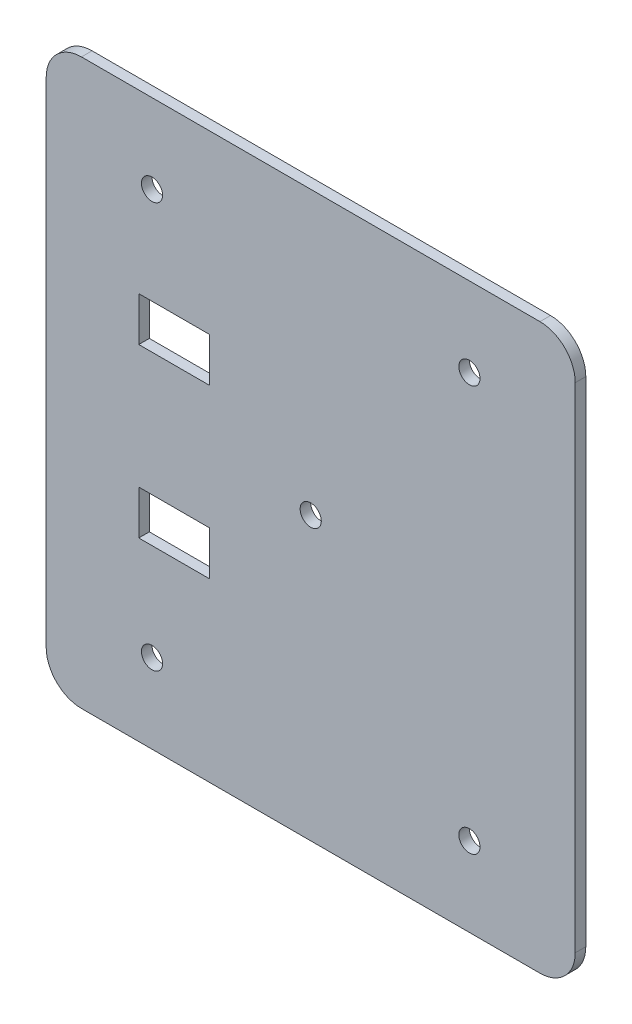
SolidWorks part; units mm, degrees
material "7075-T6, Plate (SS)"
ref_plane "Front Plane" through (0, 0, 0) normal (0, 0, 1) x (1, 0, 0)
ref_plane "Top Plane" through (0, 0, 0) normal (0, 1, 0) x (1, 0, 0)
ref_plane "Right Plane" through (0, 0, 0) normal (1, 0, 0) x (0, 0, -1)
sketch "Sketch1" plane through (0, 0, 0) normal (0, 0, 1) x (1, 0, 0)
  line L0 (-22.5, -22.5) -> (22.5, -22.5) construction
  line L1 (22.5, -22.5) -> (22.5, 22.5) construction
  line L2 (22.5, 22.5) -> (-22.5, 22.5) construction
  line L3 (-22.5, 22.5) -> (-22.5, -22.5) construction
  line L4 (22.5, 92.5) -> (22.5, 137.5) construction
  line L5 (22.5, 137.5) -> (-22.5, 137.5) construction
  line L6 (-22.5, 137.5) -> (-22.5, 92.5) construction
  line L7 (-22.5, 92.5) -> (22.5, 92.5) construction
  line L8 (-22.5, -22.5) -> (22.5, -22.5)
  line L9 (22.5, -22.5) -> (22.5, 22.5)
  line L10 (22.5, 22.5) -> (-22.5, 22.5)
  line L11 (-22.5, 22.5) -> (-22.5, -22.5)
  line L12 (22.5, 92.5) -> (22.5, 137.5)
  line L13 (22.5, 137.5) -> (-22.5, 137.5)
  line L14 (-22.5, 137.5) -> (-22.5, 92.5)
  line L15 (-22.5, 92.5) -> (22.5, 92.5)
  line L16 (-22.5, 92.5) -> (22.5, 137.5)
  line L17 (-22.5, 137.5) -> (22.5, 92.5)
  line L18 (22.5, 22.5) -> (-22.5, -22.5)
  line L19 (-22.5, 22.5) -> (22.5, -22.5)
  line L20 (75, -102.5) -> (75, 57.5)
  line L21 (-55, -102.5) -> (75, -102.5)
  line L22 (-75, -82.5) -> (-75, 197.5)
  line L23 (75, -102.5) -> (75, 217.5)
  line L24 (-55, 217.5) -> (75, 217.5)
  line L25 (-75, -102.5) -> (75, 217.5) construction
  line L26 (75, -102.5) -> (-75, 217.5) construction
  line L27 (0, 0) -> (0, 57.5)
  line L28 (75, -102.5) -> (75, 217.5)
  line L29 (75, -102.5) -> (205, -102.5)
  line L30 (75, 217.5) -> (205, 217.5)
  line L31 (225, -82.5) -> (225, 197.5)
  line L32 (165, 217.5) -> (165, 172.5)
  line L33 (165, 172.5) -> (225, 172.5)
  line L34 (225, -57.5) -> (165, -57.5)
  line L35 (165, -57.5) -> (165, -102.5)
  line L36 (-15, -102.5) -> (-15, -57.5)
  line L37 (-15, -57.5) -> (-75, -57.5)
  line L38 (-75, 172.5) -> (-15, 172.5)
  line L39 (-15, 172.5) -> (-15, 217.5)
  line L40 (-22.5, 92.5) -> (9.5, 92.5)
  line L41 (-22.5, 92.5) -> (-22.5, 117.5)
  line L42 (9.5, 92.5) -> (9.5, 117.5)
  line L43 (-22.5, 117.5) -> (9.5, 117.5)
  line L44 (-22.5, 22.5) -> (9.5, 22.5)
  line L45 (-22.5, 22.5) -> (-22.5, -2.5)
  line L46 (9.5, 22.5) -> (9.5, -2.5)
  line L47 (-22.5, -2.5) -> (9.5, -2.5)
  circle A0 centre (-15, 172.5) radius 6
  circle A1 centre (165, 172.5) radius 6
  circle A2 centre (165, -57.5) radius 6
  circle A3 centre (-15, -57.5) radius 6
  circle A4 centre (75, 57.5) radius 6
  arc A5 (-75, -82.5) -> (-55, -102.5) centre (-55, -82.5) ccw
  arc A6 (205, -102.5) -> (225, -82.5) centre (205, -82.5) ccw
  arc A7 (205, 217.5) -> (225, 197.5) centre (205, 197.5) cw
  arc A8 (-75, 197.5) -> (-55, 217.5) centre (-55, 197.5) cw
  point P7 (0, 57.5)
  point P43 (225, 217.5)
  dimension "D7" = 12
  dimension "D8" = 160
  dimension "D9" = 20
  dimension "D1" = 150
  dimension "D2" = 320
  dimension "D3" = 57.5
  dimension "D4" = 150
  dimension "D5" = 60
  dimension "D6" = 45
  dimension "D10" = 45
  dimension "D11" = 25
  dimension "D12" = 25
  dimension "D13" = 32
extrude "Boss-Extrude1" add sketch "Sketch1" along normal blind 6 contours L22 A5 L21 L36 A3 L37 | A4 L28 L24 L39 A0 L38 L22 L37 A3 L36 L21 L20 L15 L14 L13 L12 L11 L10 L9 L8 | A4 L20 L29 L35 A2 L34 L31 L33 A1 L32 L30 L28 | L29 A6 L31 L34 A2 L35 | A7 L30 L32 A1 L33 L31 | A8 L22 L38 A0 L39 L24 | L16 L43 L42 L17 L12 | L42 L15 L17 | L17 L43 L16 L13 | L14 L43 L17 | L47 L18 L8 L19 | L47 L19 L9 L18 L46 | L10 L46 L18 | L47 L11 L18 region at (0, -15.1667, 0) region at (-15.8333, -9.1667, 0) region at (16.34, -0.2688, 0) region at (13.8333, 18.1667, 0) region at (16.34, 115.2688, 0) region at (13.8333, 96.8333, 0) region at (0, 130.1667, 0) region at (-15.8333, 124.1667, 0) region at (6.2964, 57.5, 0) region at (144.3054, 57.5, 0) region at (-44.4526, -79.6196, 0) region at (194.4526, -79.6196, 0) region at (-44.4526, 194.6196, 0) region at (194.4526, 194.6196, 0)
sketch "Sketch2" plane through (0, 0, 22) normal (0, 0, 1) x (1, 0, 0)
  line L0 (17.5, 22.5) -> (-22.5, 22.5) construction
  line L1 (-22.5, 22.5) -> (-22.5, -2.5) construction
  line L2 (-22.5, -2.5) -> (17.5, -2.5) construction
  line L3 (17.5, -2.5) -> (17.5, 22.5) construction
  line L4 (17.5, 117.4998) -> (-22.5, 117.4998) construction
  line L5 (-22.5, 117.4998) -> (-22.5, 92.4998) construction
  line L6 (-22.5, 92.4998) -> (17.5, 92.4998) construction
  line L7 (17.5, 92.4998) -> (17.5, 117.4998) construction
  line L8 (17.5, 22.5) -> (-22.5, 22.5)
  line L9 (-22.5, 22.5) -> (-22.5, -2.5)
  line L10 (-22.5, -2.5) -> (17.5, -2.5)
  line L11 (17.5, -2.5) -> (17.5, 22.5)
  line L12 (17.5, 117.4998) -> (-22.5, 117.4998)
  line L13 (-22.5, 117.4998) -> (-22.5, 92.4998)
  line L14 (-22.5, 92.4998) -> (17.5, 92.4998)
  line L15 (17.5, 92.4998) -> (17.5, 117.4998)
extrude "Cut-Extrude1" cut sketch "Sketch2" against normal through all
